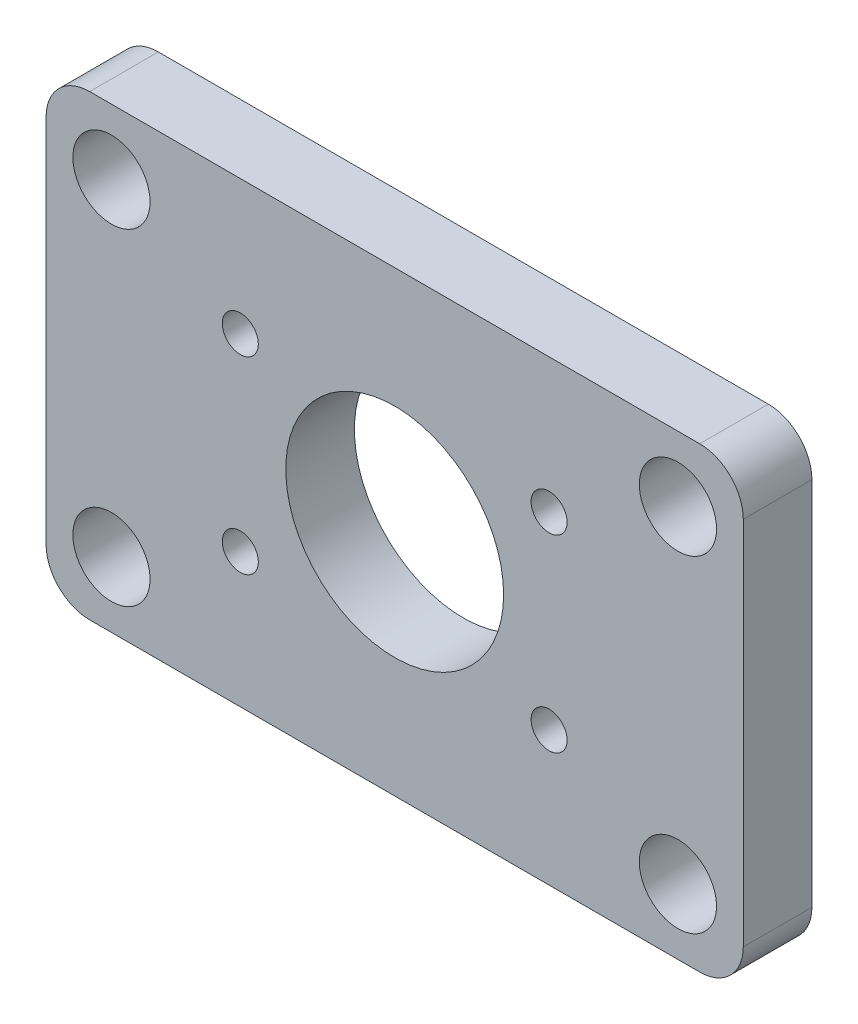
SolidWorks part; units mm, degrees
ref_plane "Front Plane" through (0, 0, 0) normal (0, 0, 1) x (1, 0, 0)
ref_plane "Top Plane" through (0, 0, 0) normal (0, 1, 0) x (1, 0, 0)
ref_plane "Right Plane" through (0, 0, 0) normal (1, 0, 0) x (0, 0, -1)
sketch "Sketch1" plane through (0, 0, 0) normal (0, 0, 1) x (1, 0, 0)
  line L0 (0, 0) -> (-20.32, 0) construction
  line L1 (20.32, -13.335) -> (-20.32, -13.335)
  line L2 (20.32, -13.335) -> (20.32, 13.335)
  line L3 (20.32, 13.335) -> (-20.32, 13.335)
  line L4 (-20.32, -13.335) -> (-20.32, 13.335)
  line L5 (20.32, -13.335) -> (-20.32, 13.335) construction
  line L6 (20.32, 13.335) -> (-20.32, -13.335) construction
  line L7 (0, 0) -> (0, 13.335) construction
  line L8 (-9.0005, 5.5004) -> (9.0005, 5.5004) construction
  line L9 (9.0005, 5.5004) -> (9.0005, -5.5004) construction
  circle A0 centre (-16.51, 9.525) radius 2.25
  circle A1 centre (16.51, 9.525) radius 2.25
  circle A2 centre (16.51, -9.525) radius 2.25
  circle A3 centre (-16.51, -9.525) radius 2.25
  circle A4 centre (-9.0005, 5.5004) radius 1.05
  circle A5 centre (9.0005, -5.5004) radius 1.05
  circle A6 centre (0, 0) radius 6.35
  circle A7 centre (-9.0005, -5.5004) radius 1.05
  circle A8 centre (9.0005, 5.5004) radius 1.05
  point P0 (0, 0)
  point P22 (0, 5.5004)
  point P24 (9.0005, 0)
  dimension "D3" = 4.5
  dimension "D6" = 2.1
  dimension "D9" = 12.7
  dimension "D1" = 26.67
  dimension "D2" = 40.64
  dimension "D4" = 19.05
  dimension "D5" = 33.02
  dimension "D7" = 18.001
  dimension "D8" = 11.0007
extrude "Boss-Extrude1" add sketch "Sketch1" along normal blind 4
fillet "Fillet1" radius 2.54 4 edges at (20.32, 13.335, 2) (20.32, -13.335, 2) (-20.32, -13.335, 2) (-20.32, 13.335, 2)
